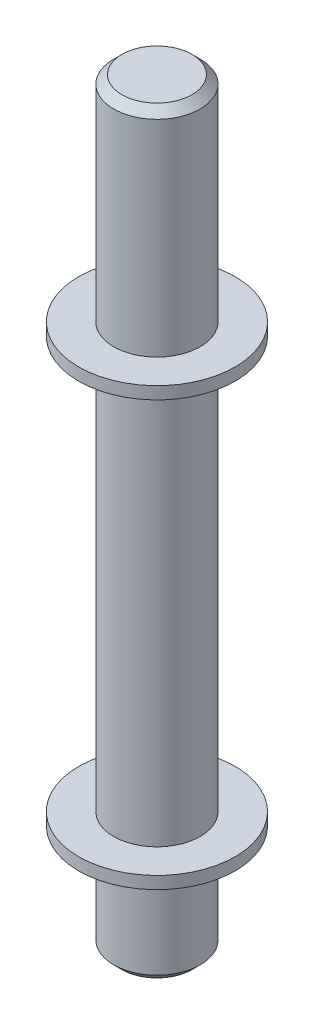
SolidWorks part; units mm, degrees
ref_plane "Front Plane" through (0, 0, 0) normal (0, 0, 1) x (1, 0, 0)
ref_plane "Top Plane" through (0, 0, 0) normal (0, 1, 0) x (1, 0, 0)
ref_plane "Right Plane" through (0, 0, 0) normal (1, 0, 0) x (0, 0, -1)
sketch "Sketch1" plane through (0, 0, 0) normal (0, 1, 0) x (1, 0, 0)
  circle A0 centre (0, 0) radius 10.5
  circle A1 centre (0, 0) radius 19
  dimension "D1" = 21
  dimension "D2" = 38
extrude "Boss-Extrude1" add sketch "Sketch1" along normal blind 26 contours A0 region at (0, 0, 0)
extrude "Boss-Extrude2" add sketch "Sketch1<3>" along normal blind 3 from surface contours A1 starting at face at (0, 26, 10.5)
sketch "Sketch1<3>" plane through (0, 0, 0) normal (0, 1, 0) x (1, 0, 0) same geometry as "Sketch1"
extrude "Boss-Extrude3" add sketch "Sketch1<4>" along normal blind 100 from surface contours A0 region at (0, 0, 0) starting at face at (0, 29, 19)
sketch "Sketch1<4>" plane through (0, 0, 0) normal (0, 1, 0) x (1, 0, 0) same geometry as "Sketch1"
extrude "Boss-Extrude4" add sketch "Sketch1<5>" along normal blind 3 from surface contours A1 starting at face at (0, 129, 10.5)
sketch "Sketch1<5>" plane through (0, 0, 0) normal (0, 1, 0) x (1, 0, 0) same geometry as "Sketch1"
extrude "Boss-Extrude5" add sketch "Sketch1<6>" along normal blind 52 from surface contours A0 region at (0, 0, 0) starting at face at (0, 132, 19)
sketch "Sketch1<6>" plane through (0, 0, 0) normal (0, 1, 0) x (1, 0, 0) same geometry as "Sketch1"
chamfer "Chamfer1" distance 2 angle 45 2 edges at (0, 0, 10.5) (0, 184, 10.5)
cosmetic thread "Cosmetic Thread1"
cosmetic thread "Cosmetic Thread2"
